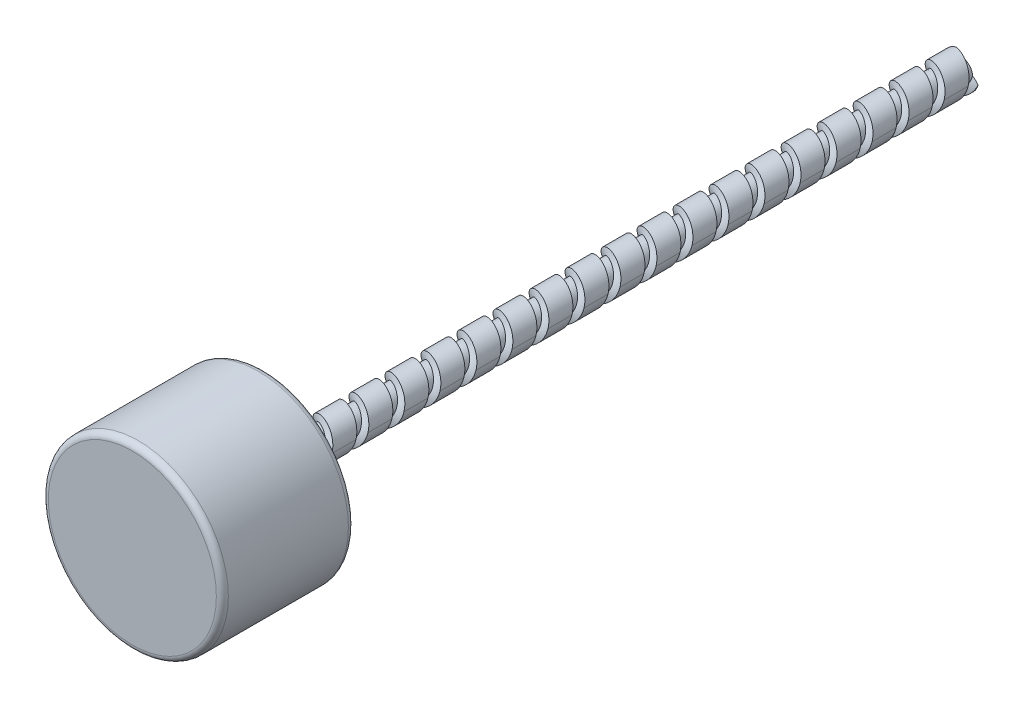
SolidWorks part; units mm, degrees
material "1023 碳钢板 (SS)"
ref_plane "前视基准面" through (0, 0, 0) normal (0, 0, 1) x (1, 0, 0)
ref_plane "上视基准面" through (0, 0, 0) normal (0, 1, 0) x (1, 0, 0)
ref_plane "右视基准面" through (0, 0, 0) normal (1, 0, 0) x (0, 0, -1)
other "Configuration Table"
sketch "草图1" plane through (0, 0, 0) normal (0, 0, 1) x (1, 0, 0)
  circle A0 centre (0, 0) radius 7.5
  dimension "D1" = 15
extrude "凸台-拉伸1" add sketch "草图1" along normal blind 11
fillet "圆角1" radius 0.5 2 edges at (7.5, 0, 0) (7.5, 0, 11)
sketch "草图2" plane through (0, 0, 0) normal (0, 0, -1) x (-1, 0, 0)
  circle A0 centre (0, 0) radius 1.5
  dimension "D1" = 3
extrude "凸台-拉伸2" add sketch "草图2" along normal blind 58
cosmetic thread "装饰螺纹线1" [suppressed] parameters "D2"=0.3
sketch "草图5" plane through (0, 0, -58) normal (0, 0, -1) x (-1, 0, 0)
  circle A0 centre (0, 0) radius 1.5
curve "螺旋线/涡状线1" pitch 3 height 57 radius 1.5 left hand yes centre (0, 0, -58) axis (0, 0, 1) start towards (0.7071, 0.7071, 0)
sketch "草图6" plane through (0, 0, 0) normal (0, 1, 0) x (1, 0, 0)
  line L0 (1.5, 54.125) -> (1.5, 55.125)
  line L1 (1.5, 55.125) -> (1, 54.975)
  line L2 (1, 54.975) -> (1, 54.275)
  line L3 (1, 54.275) -> (1.5, 54.125)
  line L4 (-0.7092, 54.625) -> (3.8675, 54.625) construction
  point P6 (3.6246, 56.5749)
  point P7 (1.5, 54.625)
  dimension "D1" = 1
  dimension "D2" = 0.7
  dimension "D3" = 0.5
sweep "切除-扫描1" cut profiles "草图6" path "螺旋线/涡状线1" align with end faces yes
